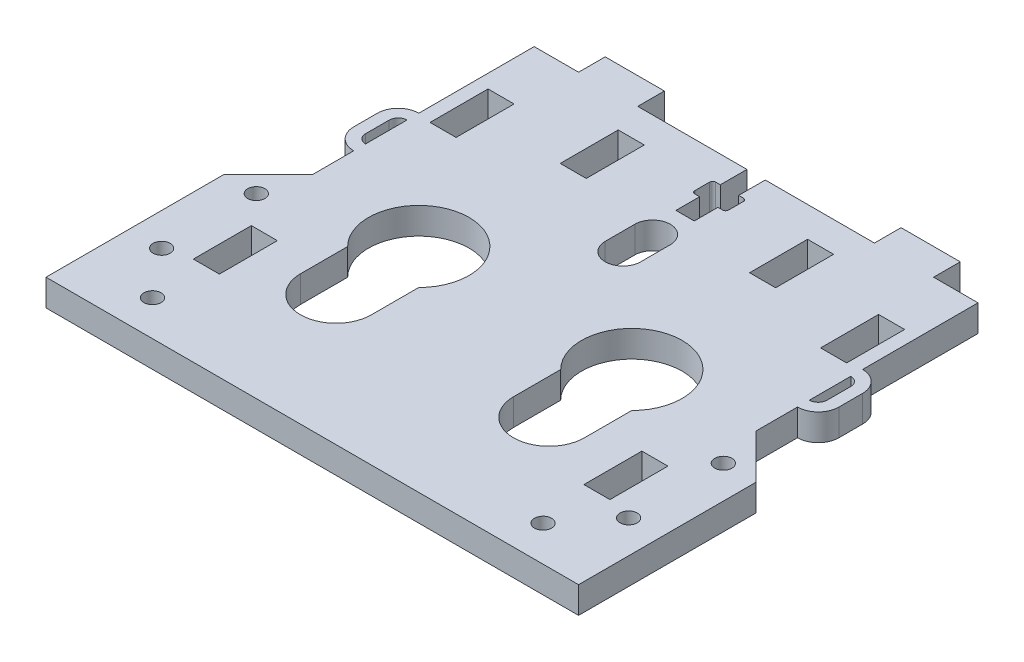
SolidWorks part; units mm, degrees
ref_plane "Front Plane" through (0, 0, 0) normal (0, 0, 1) x (1, 0, 0)
ref_plane "Top Plane" through (0, 0, 0) normal (0, 1, 0) x (1, 0, 0)
ref_plane "Right Plane" through (0, 0, 0) normal (1, 0, 0) x (0, 0, -1)
sketch "Sketch1" plane through (0, 0, 0) normal (0, 1, 0) x (1, 0, 0)
  line L1 (-37.5, 37.5) -> (37.5, 37.5)
  line L2 (-37.5, 37.5) -> (-37.5, -37.5)
  line L3 (-37.5, -37.5) -> (37.5, -37.5)
  line L4 (37.5, 37.5) -> (37.5, -37.5)
  line L5 (-37.5, 37.5) -> (37.5, -37.5) construction
  line L6 (-37.5, -37.5) -> (37.5, 37.5) construction
  point P0 (0, 0)
  dimension "D1" = 75
  dimension "D2" = 75
extrude "MainShape" add sketch "Sketch1" along normal blind 4.5
sketch "Sketch2" plane through (0, 4.5, 0) normal (0, 1, 0) x (1, 0, 0)
  line L0 (0, -37.5) -> (0, 37.5) construction
  line L1 (-37.5, -37.5) -> (37.5, -37.5) construction
  line L2 (37.5, 37.5) -> (-37.5, 37.5) construction
  line L4 (-5, 42) -> (5, 42)
  line L5 (-5, 42) -> (-5, 33)
  line L6 (-5, 33) -> (5, 33)
  line L7 (5, 42) -> (5, 33)
  line L8 (-5, 42) -> (5, 33) construction
  line L9 (-5, 33) -> (5, 42) construction
  dimension "D1" = 10
  dimension "D2" = 4.5
extrude "Tab1" [suppressed] add sketch "Sketch2" against normal through all
sketch "Sketch4" [suppressed] plane through (0, 4.5, 0) normal (0, 1, 0) x (1, 0, 0)
  line L0 (0, 42) -> (0, -37.5) construction
  line L1 (5, 42) -> (-5, 42) construction
  line L2 (-47.5, -37.5) -> (47.5, -37.5) construction
  line L3 (-40, 37.5) -> (-40, 27) construction
  line L4 (-5, 37.5) -> (-47.5, 37.5) construction
  line L5 (-38.25, 27) -> (-41.75, 27) construction
  line L6 (-41.75, 27) -> (-41.75, 37.5) construction
  line L7 (-38.25, 27) -> (-41.75, 27)
  line L8 (-41.75, 27) -> (-41.75, 29.5)
  line L9 (-41.75, 29.5) -> (-42.75, 29.5)
  line L10 (-43, 29.75) -> (-43, 33.45)
  line L11 (-42.75, 33.7) -> (-41.75, 33.7)
  line L12 (-41.75, 33.7) -> (-41.75, 37.5)
  line L13 (-41.75, 37.5) -> (-38.25, 37.5)
  line L14 (-38.25, 27) -> (-38.25, 37.5) construction
  line L15 (-38.25, 33.7) -> (-38.25, 37.5)
  line L16 (-37.25, 33.7) -> (-38.25, 33.7)
  line L17 (-37, 29.75) -> (-37, 33.45)
  line L18 (-38.25, 29.5) -> (-37.25, 29.5)
  line L19 (-38.25, 27) -> (-38.25, 29.5)
  line L20 (38.25, 27) -> (38.25, 37.5) construction
  line L21 (41.75, 27) -> (41.75, 37.5) construction
  line L22 (38.25, 27) -> (41.75, 27) construction
  line L23 (40, 37.5) -> (40, 27) construction
  line L24 (38.25, 27) -> (38.25, 29.5)
  line L25 (38.25, 29.5) -> (37.25, 29.5)
  line L26 (37, 29.75) -> (37, 33.45)
  line L27 (37.25, 33.7) -> (38.25, 33.7)
  line L28 (38.25, 33.7) -> (38.25, 37.5)
  line L29 (41.75, 37.5) -> (38.25, 37.5)
  line L30 (41.75, 33.7) -> (41.75, 37.5)
  line L31 (42.75, 33.7) -> (41.75, 33.7)
  line L32 (43, 29.75) -> (43, 33.45)
  line L33 (41.75, 29.5) -> (42.75, 29.5)
  line L34 (41.75, 27) -> (41.75, 29.5)
  line L35 (38.25, 27) -> (41.75, 27)
  arc A0 (-42.75, 29.5) -> (-43, 29.75) centre (-42.75, 29.75) cw
  arc A1 (-37, 29.75) -> (-37.25, 29.5) centre (-37.25, 29.75) cw
  arc A2 (-37.25, 33.7) -> (-37, 33.45) centre (-37.25, 33.45) cw
  arc A3 (-43, 33.45) -> (-42.75, 33.7) centre (-42.75, 33.45) cw
  arc A4 (43, 33.45) -> (42.75, 33.7) centre (42.75, 33.45) ccw
  arc A5 (37.25, 33.7) -> (37, 33.45) centre (37.25, 33.45) ccw
  arc A6 (37, 29.75) -> (37.25, 29.5) centre (37.25, 29.75) ccw
  arc A7 (42.75, 29.5) -> (43, 29.75) centre (42.75, 29.75) ccw
  point P24 (-43, 29.5)
  point P27 (-37, 29.5)
  point P30 (-37, 33.7)
  point P33 (-43, 33.7)
  point P56 (43, 33.7)
  point P57 (37, 33.7)
  point P58 (37, 29.5)
  point P59 (43, 29.5)
  dimension "D7" = 0.5
  dimension "D1" = 11
  dimension "D2" = 1.55
  dimension "D3" = 3.5
  dimension "D4" = 2.85
  dimension "D5" = 8
  dimension "D6" = 40
extrude "Cut-Extrude2" [suppressed] cut sketch "Sketch4" against normal through all
sketch "Sketch5" plane through (0, 4.5, 0) normal (0, 1, 0) x (1, 0, 0)
  line L0 (0, -37.5) -> (0, 37.5) construction
  line L1 (-37.5, -37.5) -> (37.5, -37.5) construction
  line L3 (33, 37.5) -> (33, -37.5) construction
  line L4 (37.5, 37.5) -> (-37.5, 37.5) construction
  line L5 (-33, 37.5) -> (-33, -37.5) construction
  line L6 (30.8, 27.4) -> (35.2, 27.4)
  line L7 (30.8, 27.4) -> (30.8, 17.6)
  line L8 (30.8, 17.6) -> (35.2, 17.6)
  line L9 (35.2, 27.4) -> (35.2, 17.6)
  line L10 (30.8, 27.4) -> (35.2, 17.6) construction
  line L11 (30.8, 17.6) -> (35.2, 27.4) construction
  line L12 (-30.8, 17.6) -> (-35.2, 27.4) construction
  line L13 (-30.8, 27.4) -> (-35.2, 17.6) construction
  line L14 (-35.2, 27.4) -> (-35.2, 17.6)
  line L15 (-30.8, 17.6) -> (-35.2, 17.6)
  line L16 (-30.8, 27.4) -> (-30.8, 17.6)
  line L17 (-30.8, 27.4) -> (-35.2, 27.4)
  line L18 (-37.5, 2.5) -> (37.5, 2.5) construction
  line L19 (-37.5, 37.5) -> (-37.5, -37.5) construction
  line L20 (37.5, -37.5) -> (37.5, 37.5) construction
  line L21 (-30.8, -22.4) -> (-35.2, -12.6) construction
  line L22 (-30.8, -12.6) -> (-35.2, -22.4) construction
  line L23 (30.8, -12.6) -> (35.2, -22.4) construction
  line L24 (30.8, -22.4) -> (35.2, -12.6) construction
  line L25 (-30.8, -22.4) -> (-35.2, -22.4)
  line L26 (-30.8, -22.4) -> (-30.8, -12.6)
  line L27 (-30.8, -12.6) -> (-35.2, -12.6)
  line L28 (-35.2, -22.4) -> (-35.2, -12.6)
  line L29 (35.2, -22.4) -> (35.2, -12.6)
  line L30 (30.8, -12.6) -> (35.2, -12.6)
  line L31 (30.8, -22.4) -> (30.8, -12.6)
  line L32 (30.8, -22.4) -> (35.2, -22.4)
  line L33 (-30.8, 27.4) -> (-35.2, 17.6) construction
  line L34 (-37.5, 37.5) -> (37.5, 37.5) construction
  line L35 (37.5, 37.5) -> (-37.5, 37.5) construction
  point P10 (33, 22.5)
  point P21 (-33, 22.5)
  point P36 (-33, -17.5)
  point P37 (33, -17.5)
  dimension "D1" = 33
  dimension "D2" = 9.8
  dimension "D3" = 4.4
  dimension "D4" = 15
  dimension "D5" = 40
extrude "Cut-Extrude3" cut sketch "Sketch5" against normal through all
sketch "Sketch6" plane through (0, 4.5, 0) normal (0, 1, 0) x (1, 0, 0)
  line L0 (-18, -37.5) -> (-18, 28) construction
  line L1 (-24, -15.5) -> (-24, -7.5208)
  line L3 (-37.5, -15.5) -> (37.5, -15.5) construction
  line L4 (-37.5, 37.5) -> (-37.5, -37.5) construction
  line L5 (37.5, -37.5) -> (37.5, 37.5) construction
  line L6 (37.5, 37.5) -> (-37.5, 37.5) construction
  line L7 (-37.5, -37.5) -> (37.5, -37.5) construction
  line L8 (-12, -15.5) -> (-12, -7.5208)
  line L9 (-37.5, 37.5) -> (37.5, 37.5) construction
  arc A0 (-24, -15.5) -> (-12, -15.5) centre (-18, -15.5) ccw
  arc A2 (-12, -7.5208) -> (-24, -7.5208) centre (-18, -1.5) ccw
  dimension "D1" = 12
  dimension "D6" = 8.5
  dimension "D2" = 53
  dimension "D3" = 0
  dimension "D5" = 0
  dimension "D7" = 14
  dimension "D4" = 18
extrude "Cut-Extrude4" cut sketch "Sketch6" against normal through all
sketch "Sketch13" plane through (0, 4.5, 0) normal (0, 1, 0) x (1, 0, 0)
  line L0 (-37.5, 0) -> (-45, -7.5)
  line L1 (-37.5, 37.5) -> (-37.5, -37.5) construction
  line L2 (-45, -7.5) -> (-45, -37.5)
  line L3 (-45, -37.5) -> (-37.5, -37.5)
  line L4 (-37.5, -37.5) -> (-37.5, 0)
  line L5 (0, 37.5) -> (0, -37.5) construction
  line L6 (37.5, 37.5) -> (-37.5, 37.5) construction
  line L7 (-37.5, -37.5) -> (37.5, -37.5) construction
  line L8 (37.5, -37.5) -> (37.5, 0)
  line L9 (45, -37.5) -> (37.5, -37.5)
  line L10 (45, -7.5) -> (45, -37.5)
  line L11 (37.5, 0) -> (45, -7.5)
  line L12 (-37.5, -37.5) -> (-37.5, 0)
  line M23 (37.5, -37.5) -> (37.5, 37.5)
  line M25 (-37.5, 37.5) -> (-37.5, -37.5)
  dimension "D1" = 45
  dimension "D2" = 30
extrude "Boss-Extrude2" add sketch "Sketch13" against normal through all contours L2 L3 L0 M25 | L11 L9 L10 M23 region at (-41.1111, 4.5, 20.5556) region at (41.1111, 4.5, 20.5556)
sketch "Sketch8" plane through (0, 4.5, 0) normal (0, 1, 0) x (1, 0, 0)
  line L0 (-18, -9.5) -> (-18, -21.5) construction
  line L1 (-18, -15.5) -> (-39.46, -15.5) construction
  line L2 (-39.46, -23.5) -> (-39.46, -7.5) construction
  line L3 (-18, -21.5) -> (-18, -9.5) construction
  circle A0 centre (-39.46, -7.5) radius 1.45
  circle A1 centre (-18, -15.5) radius 6 construction
  circle A2 centre (-39.46, -23.5) radius 1.45
  dimension "D3" = 2.9
  dimension "D1" = 0
  dimension "D2" = 8
  dimension "D4" = 21.46
extrude "Cut-Extrude6" cut sketch "Sketch8" against normal through all
mirror "Mirror1" about plane through (0, 0, 0) normal (1, 0, 0) of "Cut-Extrude6", "Cut-Extrude4"
sketch "Sketch11" plane through (0, 4.5, 0) normal (0, 1, 0) x (1, 0, 0)
  line L0 (0, 37.5) -> (0, -37.5) construction
  line L1 (37.5, 37.5) -> (-37.5, 37.5) construction
  line L2 (-45, -37.5) -> (45, -37.5) construction
  line L3 (-25, 42) -> (-25, 37.5) construction
  line L4 (-30, 37.5) -> (-20, 37.5)
  line L5 (-30, 37.5) -> (-30, 42)
  line L6 (-30, 42) -> (-20, 42)
  line L7 (-20, 37.5) -> (-20, 42)
  line L8 (25, 42) -> (25, 37.5) construction
  line L9 (20, 37.5) -> (20, 42)
  line L10 (30, 42) -> (20, 42)
  line L11 (30, 37.5) -> (30, 42)
  line L12 (30, 37.5) -> (20, 37.5)
  dimension "D1" = 10
  dimension "D2" = 4.5
  dimension "D3" = 25
extrude "RearTabs" add sketch "Sketch11" against normal through all
sketch "Sketch12" plane through (0, 4.5, 0) normal (0, 1, 0) x (1, 0, 0)
  line L0 (0, 0) -> (0, 37.5) construction
  line L1 (20, 37.5) -> (-20, 37.5) construction
  line L2 (1.55, 37.5) -> (-1.55, 37.5)
  line L3 (-1.55, 37.5) -> (-1.55, 33)
  line L4 (-1.55, 33) -> (-2.35, 33)
  line L5 (-2.85, 32.5) -> (-2.85, 30)
  line L6 (-2.35, 29.5) -> (-1.55, 29.5)
  line L7 (-1.55, 29.5) -> (-1.55, 25.5)
  line L8 (-1.55, 25.5) -> (1.55, 25.5)
  line L9 (1.55, 29.5) -> (1.55, 25.5)
  line L10 (2.35, 29.5) -> (1.55, 29.5)
  line L11 (2.85, 32.5) -> (2.85, 30)
  line L12 (1.55, 33) -> (2.35, 33)
  line L13 (1.55, 37.5) -> (1.55, 33)
  arc A0 (-2.85, 30) -> (-2.35, 29.5) centre (-2.35, 30) ccw
  arc A1 (-2.35, 33) -> (-2.85, 32.5) centre (-2.35, 32.5) ccw
  arc A2 (2.35, 33) -> (2.85, 32.5) centre (2.35, 32.5) cw
  arc A3 (2.85, 30) -> (2.35, 29.5) centre (2.35, 30) cw
  point P14 (-2.85, 29.5)
  point P17 (-2.85, 33)
  point P25 (0, 25.5)
  point P28 (2.85, 33)
  point P29 (2.85, 29.5)
  dimension "D5" = 8
  dimension "D1" = 12
  dimension "D6" = 0.5
  dimension "D2" = 3.5
  dimension "D3" = 2.85
  dimension "D4" = 1.55
extrude "FrontScrewSlot" cut sketch "Sketch12" against normal through all
sketch "Sketch14" plane through (0, 4.5, 0) normal (0, 1, 0) x (1, 0, 0)
  line L0 (-33, 27.4) -> (-33, -37.5) construction
  line L1 (-30.8, 27.4) -> (-35.2, 27.4) construction
  line L2 (-45, -37.5) -> (45, -37.5) construction
  line L3 (-30, 37.5) -> (-37.5, 37.5) construction
  line L4 (0, 0) -> (0, -37.5) construction
  line L5 (33, 27.4) -> (33, -37.5) construction
  line L6 (-33, 27.4) -> (-33, -37.5) construction
  circle A0 centre (-33, -31.5) radius 1.45
  circle A1 centre (33, -31.5) radius 1.45
  dimension "D2" = 2.9
  dimension "D1" = 69
extrude "BraceScrews" cut sketch "Sketch14" against normal through all
sketch "Sketch15" plane through (0, 4.5, 0) normal (0, 1, 0) x (1, 0, 0)
  line L0 (0, -37.5) -> (0, 25.5) construction
  line L1 (-45, -37.5) -> (45, -37.5) construction
  line L2 (-1.55, 25.5) -> (1.55, 25.5) construction
  line L3 (16, 27.5) -> (-16, 27.5) construction
  line L4 (-1.55, 37.5) -> (-20, 37.5) construction
  line L5 (-18.2, 32.4) -> (-13.8, 32.4)
  line L6 (-18.2, 32.4) -> (-18.2, 22.6)
  line L7 (-18.2, 22.6) -> (-13.8, 22.6)
  line L8 (-13.8, 32.4) -> (-13.8, 22.6)
  line L9 (-18.2, 32.4) -> (-13.8, 22.6) construction
  line L10 (-18.2, 22.6) -> (-13.8, 32.4) construction
  line L11 (18.2, 22.6) -> (13.8, 32.4) construction
  line L12 (18.2, 32.4) -> (13.8, 22.6) construction
  line L13 (13.8, 32.4) -> (13.8, 22.6)
  line L14 (18.2, 22.6) -> (13.8, 22.6)
  line L15 (18.2, 32.4) -> (18.2, 22.6)
  line L16 (18.2, 32.4) -> (13.8, 32.4)
  point P19 (0, 27.5)
  dimension "D1" = 16
  dimension "D2" = 4.4
  dimension "D3" = 9.8
  dimension "D4" = 10
extrude "FanTabs" cut sketch "Sketch15" against normal through all
sketch "Sketch16" plane through (0, 4.5, 0) normal (0, 1, 0) x (1, 0, 0)
  line L0 (0, 0) -> (0, 25.5) construction
  line L1 (-1.55, 25.5) -> (1.55, 25.5) construction
  line L2 (0, 20) -> (0, 15) construction
  line L3 (3, 20) -> (3, 15)
  line L4 (-3, 20) -> (-3, 15)
  arc A0 (3, 20) -> (-3, 20) centre (0, 20) ccw
  arc A1 (-3, 15) -> (3, 15) centre (0, 15) ccw
  point P7 (0, 17.5)
  dimension "D1" = 3
  dimension "D2" = 20
  dimension "D3" = 5
extrude "WiringSlot" cut sketch "Sketch16" against normal through all
sketch "Sketch17" plane through (0, 4.5, 0) normal (0, 1, 0) x (1, 0, 0)
  line L0 (-37.5, 14.5) -> (-37.5, 10.5) construction
  line L3 (-37.5, 37.5) -> (-37.5, 0) construction
  line L4 (-36, 14.5) -> (-36, 10.5)
  line L5 (-39, 14.5) -> (-39, 10.5)
  line L6 (-37.5, 14.5) -> (-37.5, 10.5) construction
  line L7 (-34, 14.5) -> (-34, 10.5)
  line L8 (-41, 14.5) -> (-41, 10.5)
  line L9 (-41, 12.5) -> (-37.5, 12.5) construction
  line L10 (0, 0) -> (0, -12.1805) construction
  arc A0 (-36, 14.5) -> (-39, 14.5) centre (-37.5, 14.5) ccw
  arc A1 (-39, 10.5) -> (-36, 10.5) centre (-37.5, 10.5) ccw
  arc A2 (-34, 14.5) -> (-41, 14.5) centre (-37.5, 14.5) ccw
  arc A3 (-41, 10.5) -> (-34, 10.5) centre (-37.5, 10.5) ccw
  point P4 (-37.5, 12.5)
  point P10 (-37.5, 12.5)
  dimension "D4" = 4
  dimension "D5" = 25
  dimension "D1" = 0
  dimension "D2" = 2
  dimension "D3" = 1.5
extrude "Boss-Extrude3" add sketch "Sketch17" against normal through all
mirror "Mirror2" about plane through (0, 0, 0) normal (1, 0, 0) of "Boss-Extrude3"
equation "\"X-ROD-SPACING\"=45"
equation "\"Y-ROD-SPACING\"=75"
equation "\"Z-ROD-SPACING\"=17.5"
equation "\"Y-BED-OFFSET\"=2"
equation "\"Y-BED-ROD-INSET\"=3.5"
equation "\"Y-BED-SCREW-SPACING\"=209"
equation "\"Y-BED-SCREW-CUTOUT-SLOT-HEIGHT\"=2"
equation "\"T-SLOT-NUT-FILLET-RADIUS\"=0.5"
equation "\"T-SLOT-SCREW-SHAFT-RADIUS\"=1.55"
equation "\"T-SLOT-SCREW-SHAFT-CUTOUT-LENGTH\"=11.0"
equation "\"T-SLOT-NUT-DEPTH\"=3.5"
equation "\"T-SLOT-NUT-WIDTH\"=2.85"
equation "\"T-SLOT-NUT-END-DISTANCE\"=8"
equation "\"ACRYLIC-THICKNESS\"=10"
equation "\"ACRYLIC-THICKNESS2\"=4.5"
equation "\"ACRYLIC-TAB-CUTOUT-SIZE\"=\"ACRYLIC-THICKNESS\"+\"ACRYLIC-TAB-TOLERANCE\"*2"
equation "\"ACRYLIC-TAB-WIDTH\"=\"ACRYLIC-THICKNESS\""
equation "\"ACRYLIC-M3-HOLE\"=2.9"
equation "\"SMOOTHROD-CAP-SCREW-DISTANCE\"=20"
equation "\"FRAME-WIDTH-INNER\"=370"
equation "\"NEMA17-HOLE-SPACING\"=31"
equation "\"NEMA17-CENTRAL-CUTOUT\"=22.5"
equation "\"Z-BRACKET-REACH\"=55"
equation "\"Z-ROD-INSET\"=16"
equation "\"TOP-BRACKET-SPACING\"=40"
equation "\"SMOOTHROD-X-LENGTH\"=350"
equation "\"SMOOTHROD-Y-LENGTH\"=350"
equation "\"SMOOTHROD-Z-LENGTH\"=350"
equation "\"SMOOTHROD-TIGHTENING-HEADROOM\"=.25"
equation "\"LEADSCREW-Z-LENGTH\"=300"
equation "\"SCREW-LENGTH-FRAME\"=\"ACRYLIC-THICKNESS\" + 10"
equation "\"SCREW-LENGTH-MOTOR\"=\"ACRYLIC-THICKNESS\" + 5"
equation "\"SCREW-LENGTH-EXTRUDER\"=28"
equation "\"SCREW-HEAD-RADIUS\"=6"
equation "\"PRINTED-X-SMOOTHROD-DIAMETER\"=9.4"
equation "\"PRINTED-X-SMOOTHROD-CUTOUT\"=10"
equation "\"PRINTED-X-BASE-HEIGHT\"=10"
equation "\"PRINTED-LM8UU-CUTOUT-SIZE\"=15.5"
equation "\"PRINTED-LM8UU-CUTOUT-LENGTH\"=24.5"
equation "\"PRINTED-X-IDLER-HEIGHT\"=16"
equation "\"PSU-MOUNTING-WIDTH\"=95"
equation "\"PSU-MOUNTING-HEIGHT\"=177"
equation "\"Y-BELT-TO-ROD-DISTANCE\"=20"
equation "\"SPOOL-HOLDER-ROD-SPACING\"=150"
equation "\"ACRYLIC-X-CARRIAGE-WIDTH\"=55"
equation "\"ACRYLIC-X-CARRIAGE-HEIGHT\"=75"
equation "\"ACRYLIC-X-CARRIAGE-SCREW-SPACING-X\"=15"
equation "\"ACRYLIC-X-CARRIAGE-SCREW-SPACING-Y\"=33"
equation "\"ACRYLIC-X-CARRIAGE-CENTER-TAB-SPACING\"=14"
equation "\"D1@MainShape\" = \"ACRYLIC-THICKNESS2\""
equation "\"D1@Sketch2\"=\"ACRYLIC-TAB-WIDTH\""
equation "\"D2@Sketch2\"=\"ACRYLIC-THICKNESS2\""
equation "\"D1@Sketch4\"=\"T-SLOT-SCREW-SHAFT-CUTOUT-LENGTH\""
equation "\"D2@Sketch4\"=\"T-SLOT-SCREW-SHAFT-RADIUS\""
equation "\"D3@Sketch4\"=\"T-SLOT-NUT-DEPTH\""
equation "\"D4@Sketch4\"=\"T-SLOT-NUT-WIDTH\""
equation "\"D5@Sketch4\"=\"T-SLOT-NUT-END-DISTANCE\""
equation "\"D7@Sketch4\"=\"T-SLOT-NUT-FILLET-RADIUS\""
equation "\"ACRYLIC-X-CARRIAGE-EXTRUDER-SHELF-DEPTH\"=\"ACRYLIC-X-CARRIAGE-EXTRUDER-OFFSET\" + 28"
equation "\"ACRYLIC-X-CARRIAGE-LM8UU-CUTOUT-WIDTH\"=24.25"
equation "\"ACRYLIC-X-CARRIAGE-EXTRUDER-BRACE-SPACING\"=23"
equation "\"ACRYLIC-X-CARRIAGE-EXTRUDER-BRACE-TAB-OFFSET\"=20"
equation "\"ACRYLIC-X-CARRIAGE-EXTRUDER-BRACE-HEIGHT\"=35"
equation "\"ACRYLIC-X-CARRIAGE-EXTRUDER-BRACE-SCREW-SPACING\"=22"
equation "\"D2@Sketch5\"=\"ACRYLIC-THICKNESS2-TAB-CUTOUT-HEIGHT\""
equation "\"D3@Sketch5\"=\"ACRYLIC-THICKNESS2-TAB-CUTOUT-WIDTH\""
equation "\"D3@Sketch8\"=\"ACRYLIC-M3-HOLE\""
equation "\"ACRYLIC-X-CARRIAGE-EXTRUDER-ANGLE\"=90"
equation "\"ACRYLIC-X-CARRIAGE-EXTRUDER-OFFSET\"=26"
equation "\"ACRYLIC-TAB-TOLERANCE\"=-.05"
equation "\"ACRYLIC-X-CARRIAGE-DUAL-WIDTH-MULTIPLIER\"=1.65"
equation "\"ACRYLIC-X-CARRIAGE-DUAL-HOTEND-SPACING\"=42"
equation "\"ACRYLIC-X-CARRIAGE-DUAL-WIDTH\"=75"
equation "\"ACRYLIC-X-CARRIAGE-DUAL-HOTEND-SEPARATION\"=36"
equation "\"ACRYLIC-X-CARRIAGE-DUAL-MOUNT-PLATE-DEPTH\"=75"
equation "\"ACRYLIC-X-CARRIAGE-DUAL-MOUNT-BRACE-WIDTH\"=33"
equation "\"D1@Sketch5\"=\"ACRYLIC-X-CARRIAGE-DUAL-MOUNT-BRACE-WIDTH\""
equation "\"ACRYLIC-X-CARRIAGE-DUAL-MOUNT-SCREW-WIDTH\"=40"
equation "\"D6@Sketch4\"=\"ACRYLIC-X-CARRIAGE-DUAL-MOUNT-SCREW-WIDTH\""
equation "\"D1@Sketch1\"=\"ACRYLIC-X-CARRIAGE-DUAL-WIDTH\""
equation "\"D2@Sketch1\"=\"ACRYLIC-X-CARRIAGE-DUAL-MOUNT-PLATE-DEPTH\""
equation "\"D4@Sketch6\"=\"ACRYLIC-X-CARRIAGE-DUAL-HOTEND-SEPARATION\"/2"
equation "\"D1@Sketch11\"=\"ACRYLIC-TAB-WIDTH\""
equation "\"D2@Sketch11\"=\"ACRYLIC-THICKNESS2\""
equation "\"D1@Sketch12\"=\"T-SLOT-SCREW-SHAFT-CUTOUT-LENGTH\"+1"
equation "\"D2@Sketch12\"=\"T-SLOT-NUT-DEPTH\""
equation "\"D3@Sketch12\"=\"T-SLOT-NUT-WIDTH\""
equation "\"D4@Sketch12\"=\"T-SLOT-SCREW-SHAFT-RADIUS\""
equation "\"D5@Sketch12\"=\"T-SLOT-NUT-END-DISTANCE\""
equation "\"D6@Sketch12\"=\"T-SLOT-NUT-FILLET-RADIUS\""
equation "\"D2@Sketch14\"=\"ACRYLIC-M3-HOLE\""
equation "\"D2@Sketch15\"=\"ACRYLIC-THICKNESS2-TAB-CUTOUT-WIDTH\""
equation "\"D3@Sketch15\"=\"ACRYLIC-THICKNESS2-TAB-CUTOUT-HEIGHT\""
equation "\"KERF\"=0.05"
equation "\"PRINTED-M3-HOLE\"=3.5"
equation "\"PRINTED-M3-NUT-AF\"=6.25"
equation "\"ACRYLIC-X-CARRIAGE-LM8UU-CUTOUT-HEIGHT\"=11.0"
equation "\"ACRYLIC-X-CARRIAGE-DUAL-FAN-OFFSET\"=52"
equation "\"ACRYLIC-X-CARRIAGE-DUAL-FAN-HEIGHT\"=20"
equation "\"BLOWER-FAN-WIDTH\"=15"
equation "\"ACRYLIC-THICKNESS-TAB-CUTOUT-WIDTH\"=\"ACRYLIC-THICKNESS\"-\"KERF\"*2"
equation "\"ACRYLIC-THICKNESS-TAB-CUTOUT-HEIGHT\"=\"ACRYLIC-TAB-WIDTH\"-\"KERF\"*4"
equation "\"ACRYLIC-THICKNESS2-TAB-CUTOUT-WIDTH\"=\"ACRYLIC-THICKNESS2\"-\"KERF\"*2"
equation "\"ACRYLIC-THICKNESS2-TAB-CUTOUT-HEIGHT\"=\"ACRYLIC-TAB-WIDTH\"-\"KERF\"*4"
